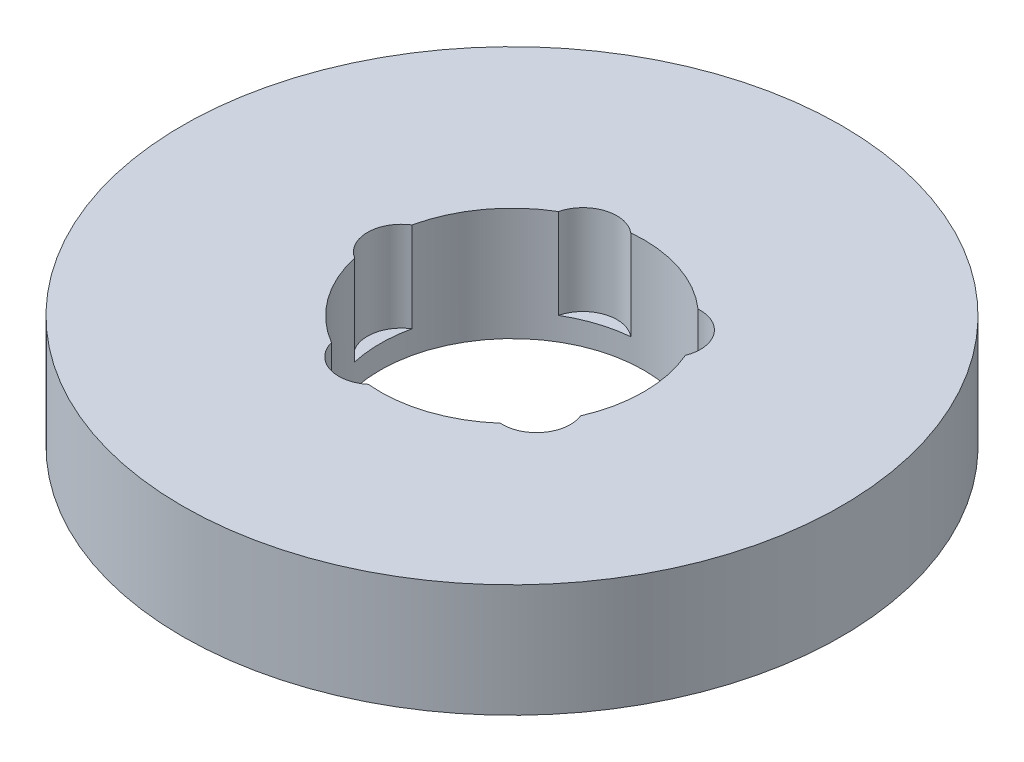
SolidWorks part; units mm, degrees
ref_plane "Front Plane" through (0, 0, 0) normal (0, 0, 1) x (1, 0, 0)
ref_plane "Top Plane" through (0, 0, 0) normal (0, 1, 0) x (1, 0, 0)
ref_plane "Right Plane" through (0, 0, 0) normal (1, 0, 0) x (0, 0, -1)
sketch "Sketch1" plane through (0, 0, 0) normal (0, 1, 0) x (1, 0, 0)
  circle A0 centre (0, 0) radius 87.5
  dimension "FLANGE_OD" = 175
extrude "Boss-Extrude1" add sketch "Sketch1" along normal blind 30
sketch "Sketch2" plane through (0, 0, 0) normal (0, 1, 0) x (1, 0, 0)
  circle A0 centre (0, 0) radius 35
  dimension "BORE_D" = 70
extrude "Cut-Extrude1" cut sketch "Sketch2" along normal through all
sketch "Sketch3" plane through (0, 30, 0) normal (0, 1, 0) x (1, 0, 0)
  circle A0 centre (0, 0) radius 29.3691 construction
  circle A1 centre (-29.3691, 0) radius 8.9984
  dimension "BOLT_D" = 17.9968
  dimension "BOLT_PCD" = 58.7382
extrude "Cut-Extrude2" cut sketch "Sketch3" against normal blind 23.8846
pattern_circular "CirPattern1" count 5 over 360 about axis through (0, 0, 0) along (0, 1, 0) of "Cut-Extrude2"
